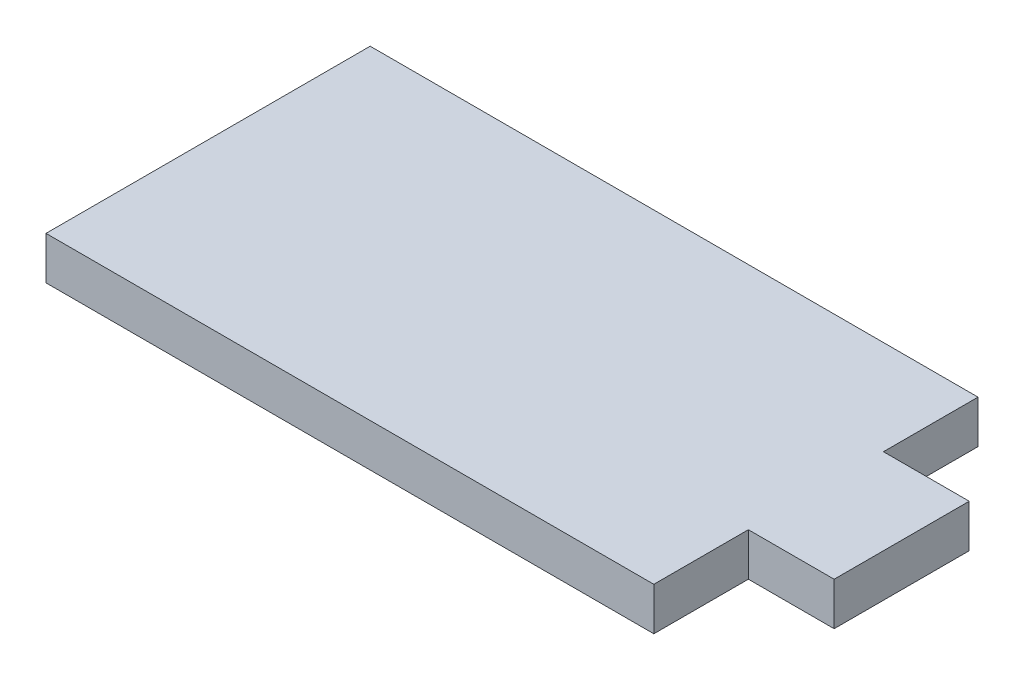
SolidWorks part; units mm, degrees
ref_plane "Front Plane" through (0, 0, 0) normal (0, 0, 1) x (1, 0, 0)
ref_plane "Top Plane" through (0, 0, 0) normal (0, 1, 0) x (1, 0, 0)
ref_plane "Right Plane" through (0, 0, 0) normal (1, 0, 0) x (0, 0, -1)
sketch "Sketch1" plane through (0, 0, 0) normal (0, 1, 0) x (1, 0, 0)
  line L0 (-22.5, 7) -> (22.5, 7)
  line L1 (22.5, 7) -> (22.5, 0)
  line L2 (22.5, 0) -> (28.85, 0)
  line L3 (28.85, 0) -> (28.85, -10)
  line L4 (28.85, -10) -> (22.5, -10)
  line L5 (22.5, -10) -> (22.5, -17)
  line L6 (22.5, -17) -> (-22.5, -17)
  line L7 (-22.5, -17) -> (-22.5, -10)
  line L8 (-22.5, -10) -> (-28.85, -10)
  line L9 (-28.85, -10) -> (-28.85, 0)
  line L10 (-28.85, 0) -> (-22.5, 0)
  line L11 (-22.5, 0) -> (-22.5, 7)
  line L12 (-22.5, 0) -> (-22.5, -10) construction
  point P11 (0, 7)
  point P14 (-28.85, -5)
  dimension "D1" = 6.35
  dimension "D2" = 10
  dimension "D3" = 45
  dimension "D4" = 24
extrude "Boss-Extrude1" add sketch "Sketch1" along normal blind 3.175 contours L11 L12 L7 L6 L5 L4 L3 L2 L1 L0 region at (1.4258, 0, 5)
equation "\"length\" = 24mm"
equation "\"w_mach\"= 45mm"
equation "\"w_tab\" = 10mm"
equation "\"t_wood\"= 0.125in"
equation "\"t_side\"= 0.25in"
equation "\"D1@Sketch1\"=\"t_side\""
equation "\"D2@Sketch1\"=\"w_tab\""
equation "\"D3@Sketch1\"=\"w_mach\""
equation "\"D4@Sketch1\"=\"length\""
equation "\"D1@Boss-Extrude1\"=\"t_wood\""
